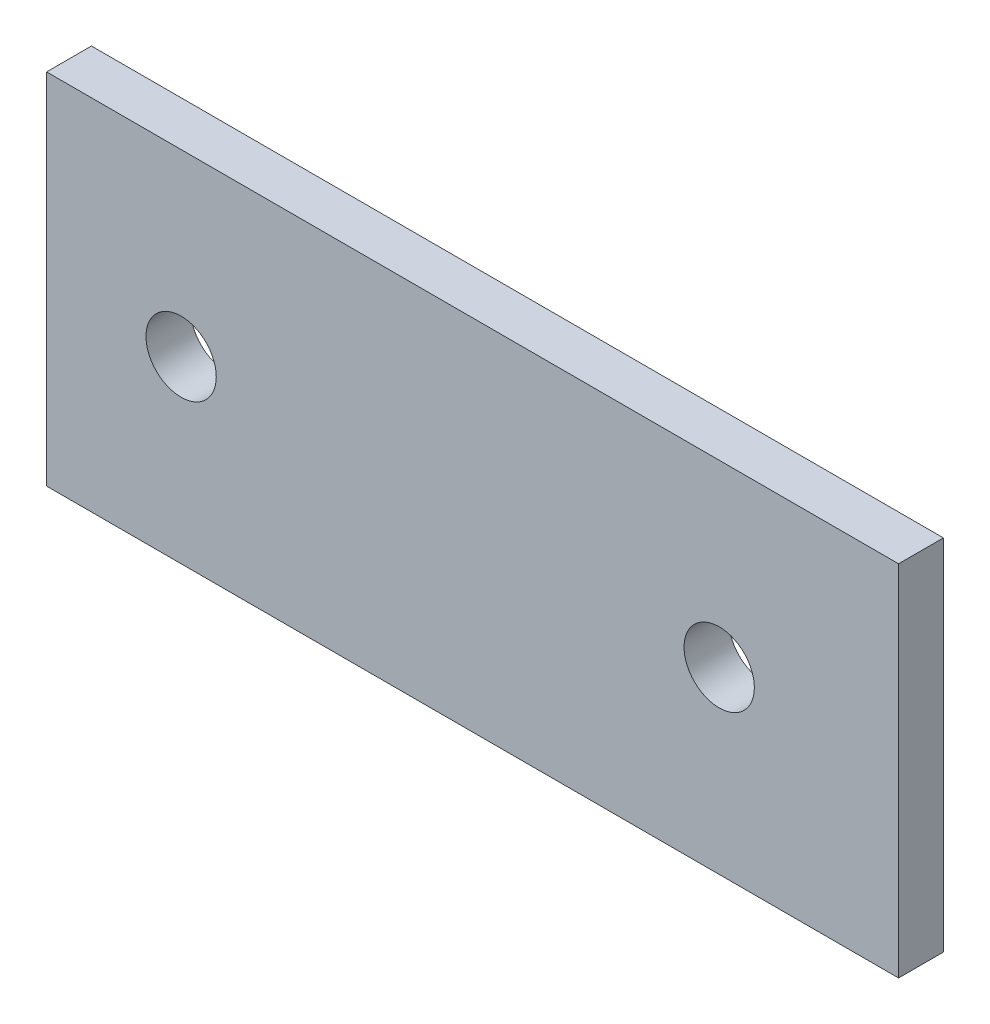
SolidWorks part; units mm, degrees
ref_plane "Front Plane" through (0, 0, 0) normal (0, 0, 1) x (1, 0, 0)
ref_plane "Top Plane" through (0, 0, 0) normal (0, 1, 0) x (1, 0, 0)
ref_plane "Right Plane" through (0, 0, 0) normal (1, 0, 0) x (0, 0, -1)
sketch "Sketch1" plane through (0, 0, 0) normal (0, 0, 1) x (1, 0, 0)
  line L1 (-30.1625, -12.7) -> (30.1625, -12.7)
  line L2 (-30.1625, -12.7) -> (-30.1625, 12.7)
  line L3 (-30.1625, 12.7) -> (30.1625, 12.7)
  line L4 (30.1625, -12.7) -> (30.1625, 12.7)
  line L5 (-30.1625, -12.7) -> (30.1625, 12.7) construction
  line L6 (-30.1625, 12.7) -> (30.1625, -12.7) construction
  circle A0 centre (-20.6375, 0) radius 2.4892
  circle A1 centre (17.4625, 0) radius 2.4892
  point P0 (0, 0)
  point P8 (-30.1625, 0)
  dimension "D4" = 4.9784
  dimension "D1" = 60.325
  dimension "D2" = 25.4
  dimension "D3" = 9.525
  dimension "D5" = 12.7
extrude "Boss-Extrude1" add sketch "Sketch1" along normal mid plane 3.175
